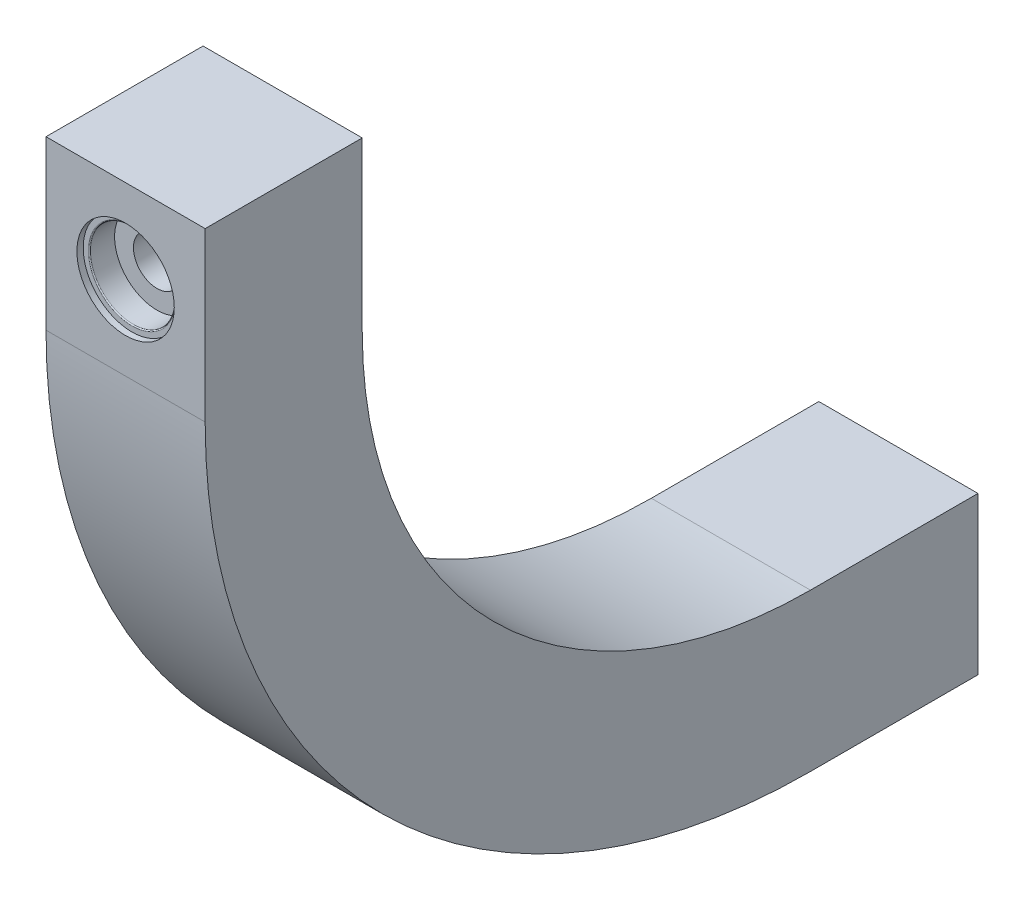
SolidWorks part; units mm, degrees
ref_plane "Front Plane" through (0, 0, 0) normal (0, 0, 1) x (1, 0, 0)
ref_plane "Top Plane" through (0, 0, 0) normal (0, 1, 0) x (1, 0, 0)
ref_plane "Right Plane" through (0, 0, 0) normal (1, 0, 0) x (0, 0, -1)
ref_axis "Z" through (0, 0, 109.5585) along (0, 0, -1)
ref_axis "X" through (8.36, 0, 0) along (-1, 0, 0)
sketch "Sketch4" plane through (0, 0, 0) normal (0, 0, 1) x (1, 0, 0)
  circle A0 centre (0, 0) radius 49.8046 construction
  dimension "D1" = 99.6092
sketch "Sketch5" plane through (0, 0, 0) normal (1, 0, 0) x (0, 0, -1)
  line L0 (-50.8046, 8) -> (-50.8046, 0)
  line L1 (-50.8046, 0) -> (-50.8046, -8)
  line L2 (-65.8046, -8) -> (-65.8046, 8)
  line L6 (-65.8046, 8) -> (-50.8046, 8)
  line L12 (-109.5585, 0) -> (-13.0351, 0) construction
  line L13 (0, 0) -> (-14.9091, -14.9091) construction
  line L14 (0, 0) -> (7.0065, 0) construction
  line L15 (0, -50.8046) -> (-8, -50.8046)
  line L16 (8, -50.8046) -> (0, -50.8046)
  line L17 (-8, -65.8046) -> (8, -65.8046)
  line L18 (8, -65.8046) -> (8, -50.8046)
  circle A0 centre (0, 0) radius 14 construction
  arc A1 (-50.8046, -8) -> (-8, -50.8046) centre (-8, -8) ccw
  arc A2 (-65.8046, -8) -> (-8, -65.8046) centre (-8, -8) ccw
  point P2 (9.4307, -21)
  point P4 (0, -2.1363)
  dimension "D1" = 28
  dimension "D4" = 8
  dimension "D2" = 45
  dimension "D3" = 15
  dimension "D5" = 50.8046
sketch "Sketch6" plane through (0, 0, 0) normal (0, 1, 0) x (1, 0, 0)
  circle A0 centre (0, 0) radius 49.8046 construction
  dimension "D1" = 99.6092
extrude "Boss-Extrude1" add sketch "Sketch5" along normal blind 7.6 and the other way blind 7.6
sketch "Sketch7" plane through (0, 0, 0) normal (0, 0, 1) x (1, 0, 0)
  circle A0 centre (0, 0) radius 2.25
  dimension "D1" = 4.5
extrude "Cut-Extrude1" cut sketch "Sketch7" along normal through all
ref_axis "Y" through (0, -9.3489, 0) along (0, -1, 0)
sketch "Sketch16" plane through (0, 0, 0) normal (1, 0, 0) x (0, 0, -1)
  line L0 (0, -66.8046) -> (0, 0) construction
  dimension "D1" = 66.8046
ref_plane "Plane1" through (0, -66.8046, 0) normal (0, 1, 0) x (1, 0, 0)
ref_axis "CX" through (0, -66.8046, 4.4) along (0, 0, -1)
ref_plane "Plane2" through (0, 0, 0) normal (0, 0, -1) x (0, 1, 0)
ref_plane "Plane3" through (0, 0, 0) normal (1, 0, 0) x (0, 0, -1)
ref_axis "CZ" through (0, -8.7018, 0) along (0, -1, 0)
ref_axis "CY" through (-0.6471, -66.8046, 0) along (1, 0, 0)
ref_point "CO"
sketch "Sketch15" plane through (0, -65.8046, 0) normal (0, -1, 0) x (1, 0, 0)
  circle A0 centre (0, 0) radius 2.05
  dimension "D1" = 4.1
extrude "Cut-Extrude11" cut sketch "Sketch15" against normal blind 10
sketch "Sketch18" plane through (0, 0, 0) normal (1, 0, 0) x (0, 0, -1)
  line L0 (-65.8046, 4.65) -> (-65.8046, 0)
  line L1 (-65.8046, 0) -> (-62.8046, 0)
  line L2 (-62.8046, 0) -> (-62.8046, 4.05)
  line L3 (-62.8046, 4.05) -> (-65.1046, 4.05)
  line L4 (-65.2046, 4.15) -> (-65.2046, 4.65)
  line L5 (-65.2046, 4.65) -> (-65.8046, 4.65)
  line L6 (-68.6876, 0) -> (-58.3046, 0) construction
  line L7 (-58.3046, 0) -> (-58.3046, 8) construction
  line L8 (-51.4046, 4.65) -> (-50.8046, 4.65)
  line L9 (-51.4046, 4.15) -> (-51.4046, 4.65)
  line L10 (-53.8046, 4.05) -> (-51.5046, 4.05)
  line L11 (-53.8046, 0) -> (-53.8046, 4.05)
  line L12 (-50.8046, 0) -> (-53.8046, 0)
  line L13 (-50.8046, 4.65) -> (-50.8046, 0)
  line L14 (-109.5585, 0) -> (-13.0351, 0) construction
  line L15 (-65.8046, 8) -> (-50.8046, 8) construction
  line L16 (-65.8046, -8) -> (-65.8046, 8) construction
  arc A0 (-65.1046, 4.05) -> (-65.2046, 4.15) centre (-65.1046, 4.15) cw
  arc A1 (-51.5046, 4.05) -> (-51.4046, 4.15) centre (-51.5046, 4.15) ccw
  point P23 (-65.2046, 4.05)
  point P26 (-51.4046, 4.05)
  dimension "D5" = 0.1
  dimension "D6" = 0.1
  dimension "D1" = 0.6
  dimension "D2" = 8.1
  dimension "D3" = 3
  dimension "D4" = 4.65
revolve "Cut-Revolve1" cut sketch "Sketch18" angle 360 about axis through (0, 0, 109.5585) along (0, 0, -1)
equation "\"rbracket-width\"= \"L2Thickness\" + 0.2"
equation "\"EyeCaptureRadius\"= ( \"EyeDiameter\" + \"EyeClearance\" ) / 2"
equation "\"rbracket_planetocenterline_dist\"= \"BasePlaneDistance\""
equation "\"EyeDiameter\" = 99.60916292"
equation "\"BasePlaneDistance\" = \"EyeDiameter\"/2+\"L2Thickness\"+\"EyeClearance\""
equation "\"EyeClearance\" = 2"
equation "\"D1@Sketch4\"=\"EyeDiameter\""
equation "\"D1@Sketch6\"=\"EyeDiameter\""
equation "\"D1@Boss-Extrude1\"=\"rbracket-width\"/2"
equation "\"D2@Boss-Extrude1\"=\"rbracket-width\"/2"
equation "\"L2Thickness\" = 3.75 * \"shaft_diameter\""
equation "\"D3@Sketch5\"=\"L2Thickness\""
equation "\"D5@Sketch5\"=(\"EyeDiameter\"+\"EyeClearance\")/2"
equation "\"BearingThickness\"= 6"
equation "\"BearingOD\"=4.5"
equation "\"OuterBearingProudDistance\"= 0"
equation "\"FlangeOD\"=7.5"
equation "\"FlangeThickness\"= 0.75"
equation "\"PrinterFilamentThickness\"= 0.1'For setting distances for things like pressfits"
equation "\"ApplyPrinterOffset\"= 1'Set to 0 for line-to-line. Set to 1 for applying guestimate dimensions to make the printer produce good parts"
equation "\"D1@Cut-Extrude11\"=\"shaft_diameter\"*2.5"
equation "\"D1@Sketch16\"=\"BasePlaneDistance\""
equation "\"D2@Sketch18\"=\"ApplyPrinterOffset\"*\"PrinterFilamentThickness\" + 8"
equation "\"D4@Sketch18\"=4.6 + \"ApplyPrinterOffset\"*\"PrinterFilamentThickness\"/2"
equation "\"L2_ID\" = 20"
equation "\"vx\" = 50"
equation "\"vy\" = 10"
equation "\"vz\" = 100"
equation "\"parametric_end\" = 1"
equation "\"Rw_3_xx\" = -(\"vz\")/sqr((\"vx\")^2 + (\"vz\")^2)"
equation "\"Rw_3_xy\" = 0"
equation "\"Rw_3_xz\" = (\"vx\")/sqr((\"vx\")^2 + (\"vz\")^2)"
equation "\"Rw_3_zx\" = (\"vx\")/sqr((\"vx\")^2 + (\"vy\")^2 + (\"vz\")^2)"
equation "\"Rw_3_zy\" = (\"vy\")/sqr((\"vx\")^2 + (\"vy\")^2 + (\"vz\")^2)"
equation "\"Rw_3_zz\" = (\"vz\")/sqr((\"vx\")^2 + (\"vy\")^2 + (\"vz\")^2)"
equation "\"Rw_3_yx\" = (\"vx\")*(\"vy\")/sqr((\"vx\")^4 + (\"vx\")^2*(\"vy\")^2 + 2*(\"vx\")^2*(\"vz\")^2 + (\"vy\")^2*(\"vz\")^2 + (\"vz\")^4)"
equation "\"Rw_3_yy\" = -sqr((\"vx\")^2 + (\"vz\")^2)/sqr((\"vx\")^2 + (\"vy\")^2 + (\"vz\")^2)"
equation "\"Rw_3_yz\" = (\"vy\")*(\"vz\")/sqr((\"vx\")^4 + (\"vx\")^2*(\"vy\")^2 + 2*(\"vx\")^2*(\"vz\")^2 + (\"vy\")^2*(\"vz\")^2 + (\"vz\")^4)"
equation "\"O2Targx\" = -\"BasePlaneDistance\"*(\"vx\")*(\"vy\")/sqr((\"vx\")^4 + (\"vx\")^2*(\"vy\")^2 + 2*(\"vx\")^2*(\"vz\")^2 + (\"vy\")^2*(\"vz\")^2 + (\"vz\")^4)"
equation "\"O2Targy\" = \"BasePlaneDistance\"*sqr((\"vx\")^2 + (\"vz\")^2)/sqr((\"vx\")^2 + (\"vy\")^2 + (\"vz\")^2)"
equation "\"O2Targz\" = -\"BasePlaneDistance\"*(\"vy\")*(\"vz\")/sqr((\"vx\")^4 + (\"vx\")^2*(\"vy\")^2 + 2*(\"vx\")^2*(\"vz\")^2 + (\"vy\")^2*(\"vz\")^2 + (\"vz\")^4)"
equation "\"O2Targx_0\" = -(\"BasePlaneDistance\")*sqr((\"vx\")^2 + (\"vz\")^2)/sqr((\"vx\")^2 + (\"vy\")^2 + (\"vz\")^2)"
equation "\"O2Targy_0\" = -(\"BasePlaneDistance\")*(\"vy\")*(\"vz\")/sqr((\"vx\")^4 + (\"vx\")^2*(\"vy\")^2 + 2*(\"vx\")^2*(\"vz\")^2 + (\"vy\")^2*(\"vz\")^2 + (\"vz\")^4)"
equation "\"O2Targz_0\" = (\"BasePlaneDistance\")*(\"vx\")*(\"vy\")/sqr((\"vx\")^4 + (\"vx\")^2*(\"vy\")^2 + 2*(\"vx\")^2*(\"vz\")^2 + (\"vy\")^2*(\"vz\")^2 + (\"vz\")^4) + (\"BasePlaneDistance\")"
equation "\"theta2_s1\" = arcsin(((\"BasePlaneDistance\") - (\"O2Targz_0\"))/(\"BasePlaneDistance\")) + pi"
equation "\"theta2_s2\" = -arcsin(((\"BasePlaneDistance\") - (\"O2Targz_0\"))/(\"BasePlaneDistance\"))"
equation "\"theta1_s1\" = arcsin((\"O2Targy_0\")/((\"BasePlaneDistance\")*cos((\"Theta2\")))) + pi"
equation "\"theta1_s2\" = -arcsin((\"O2Targy_0\")/((\"BasePlaneDistance\")*cos((\"Theta2\"))))"
equation "\"theta1_s3\" = -arccos(-(\"O2Targx_0\")/((\"BasePlaneDistance\")*cos((\"Theta2\")))) + 2*pi"
equation "\"theta1_s4\" = arccos(-(\"O2Targx_0\")/((\"BasePlaneDistance\")*cos((\"Theta2\"))))"
equation "\"Theta1\" = \"theta1_s2\" 'so far, theta1_s1 and theta1_s4 have agreed, and they agree with the sw constraint solver"
equation "\"Theta2\" = \"theta2_s2\""
equation "\"o2_x\" = -(\"BasePlaneDistance\")*cos((\"Theta1\"))*cos((\"Theta2\"))"
equation "\"o2_y\" = -(\"BasePlaneDistance\")*sin((\"Theta1\"))*cos((\"Theta2\"))"
equation "\"o2_z\" = (\"BasePlaneDistance\")*(sin((\"Theta2\")) + 1)"
equation "\"o1_x\" = (\"BasePlaneDistance\")*sin((\"Theta1\"))"
equation "\"o1_y\" = -(\"BasePlaneDistance\")*cos((\"Theta1\"))"
equation "\"o1_z\" = (\"BasePlaneDistance\")"
equation "\"Actuator1_Theta\" = atn(\"vx\"/\"vz\") 'ik solution for the single link joint"
equation "\"Actuator2_Theta\" = \"Theta1\"  'ik solution for the double link joint"
equation "\"MotorBaseThickness\" = 3 "
equation "\"BaseThickness\" = 3 "
equation "\"EncoderToMagnetAirgap\" = 1 'Encoder to magnet airgap"
equation "\"EncoderHeight\" = 1.192  'Height of the encoder"
equation "\"MagnetThickness\" = 0.5  'Magnet thickness"
equation "\"pcb_thickness\" = 1.6  'Thickness of the PCB"
equation "\"pcb_outer_diameter\" = 32 'the OD of the pcb"
equation "\"shaft_diameter\" = 4"
equation "\"D1@Sketch15\"=\"shaft_diameter\"+\"ApplyPrinterOffset\"*\"PrinterFilamentThickness\""
